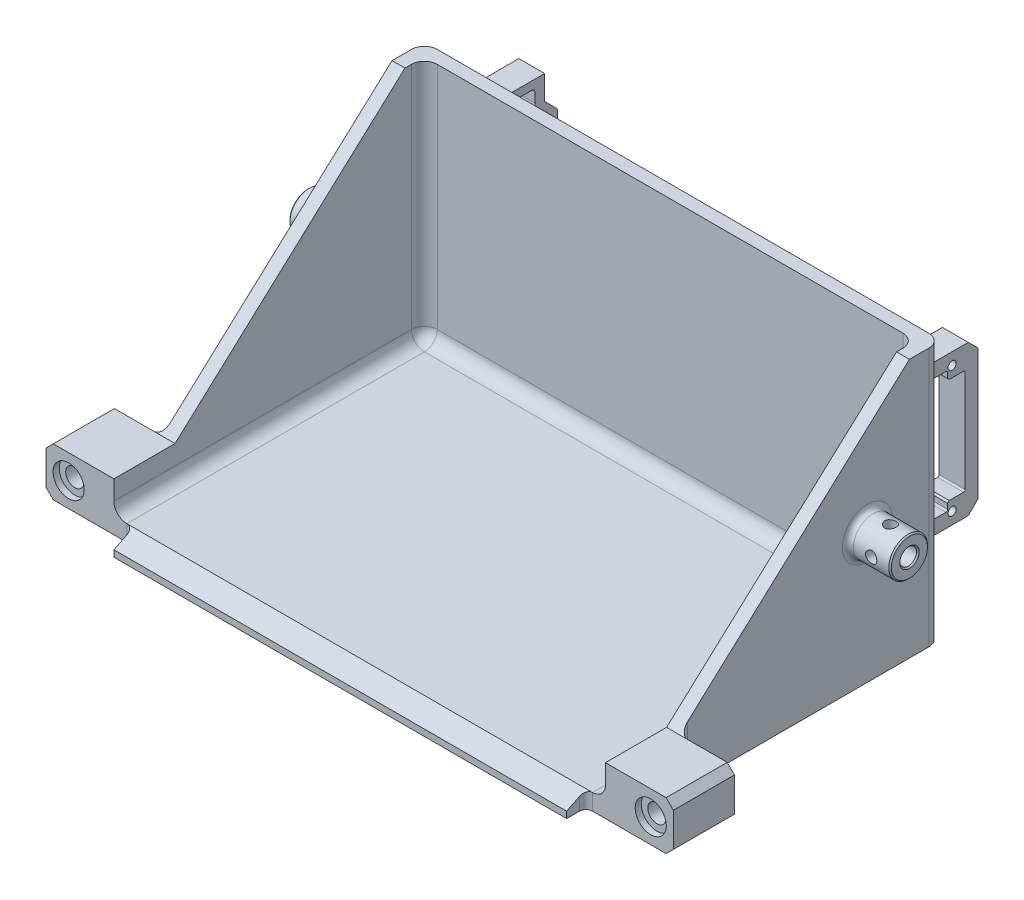
SolidWorks part; units mm, degrees
material "PLA"
ref_plane "Front Plane" through (0, 0, 0) normal (0, 0, 1) x (1, 0, 0)
ref_plane "Top Plane" through (0, 0, 0) normal (0, 1, 0) x (1, 0, 0)
ref_plane "Right Plane" through (0, 0, 0) normal (1, 0, 0) x (0, 0, -1)
sketch "Sketch1" plane through (0, 0, 0) normal (0, 1, 0) x (1, 0, 0)
  line L1 (-101.6, 63.5) -> (101.6, 63.5)
  line L2 (-101.6, 63.5) -> (-101.6, -63.5)
  line L3 (-101.6, -63.5) -> (101.6, -63.5)
  line L4 (101.6, 63.5) -> (101.6, -63.5)
  line L5 (-101.6, 63.5) -> (101.6, -63.5) construction
  line L6 (-101.6, -63.5) -> (101.6, 63.5) construction
  point P0 (0, 0)
  dimension "D1" = 203.2
  dimension "D2" = 127
extrude "Bucket_Base" add sketch "Sketch1" along normal mid plane 6.35
sketch "Sketch3" plane through (-101.6, 0, 0) normal (-1, 0, 0) x (0, 0, 1)
  line L0 (-63.5, 3.175) -> (-63.5, 98.425)
  line L1 (-63.5, 98.425) -> (-50.8, 98.425)
  line L3 (63.5, 3.175) -> (-63.5, 3.175)
  line L4 (-63.5, -3.175) -> (63.5, -3.175) construction
  line L5 (-50.8, 98.425) -> (39.497, 15.875)
  line L6 (39.497, 15.875) -> (63.5, 15.875)
  line L7 (63.5, 15.875) -> (63.5, 3.175)
  dimension "D1" = 101.6
  dimension "D2" = 12.7
  dimension "D3" = 19.05
  dimension "D4" = 24.003
extrude "Bucket_Sides" add sketch "Sketch3" against normal blind 5.08
mirror "Mirror1" about plane through (0, 0, 0) normal (1, 0, 0) of "Bucket_Sides"
sketch "Sketch4" plane through (0, 3.175, 0) normal (0, 1, 0) x (1, 0, 0)
  line L0 (-96.52, 63.5) -> (96.52, 63.5)
  line L1 (96.52, 63.5) -> (96.52, 58.42)
  line L2 (96.52, 58.42) -> (-96.52, 58.42)
  line L3 (-96.52, 58.42) -> (-96.52, 63.5)
  dimension "D1" = 5.08
extrude "Bucket_RearWall" add sketch "Sketch4" along normal up to surface (95.25 mm away) up to face at (-99.06, 98.425, -57.15)
sketch "Sketch6" plane through (101.6, 0, 0) normal (1, 0, 0) x (0, 0, -1)
  line L0 (-63.5, -3.175) -> (63.5, -3.175) construction
  line L2 (63.5, 98.425) -> (63.5, -3.175) construction
  circle A0 centre (34.29, 47.625) radius 3.2893
  circle A1 centre (34.29, 47.625) radius 7.62
  dimension "D1" = 6.5786
  dimension "D2" = 15.24
  dimension "D3" = 50.8
  dimension "D4" = 29.21
extrude "Shaft_Joint" add sketch "Sketch6" along normal blind 16.51
mirror "Mirror2" about plane through (0, 0, 0) normal (1, 0, 0) of "Shaft_Joint"
fillet "Fillet4" radius 2.159 2 edges at (101.6, 47.625, -26.67) (-101.6, 47.625, -41.91)
chamfer "Chamfer1" distance 0.508 angle 45 4 edges at (118.11, 47.625, -37.5793) (118.11, 47.625, -41.91) (-118.11, 47.625, -37.5793) (-118.11, 47.625, -41.91)
ref_plane "setscrew_lhs_plane" through (0, 55.245, 0) normal (0, 1, 0) x (1, 0, 0)
sketch "Sketch7" plane through (0, 55.245, 0) normal (0, 1, 0) x (1, 0, 0)
  line L0 (103.759, 26.67) -> (117.602, 26.67) construction
  line L1 (117.602, 41.91) -> (103.759, 41.91) construction
  line L2 (103.759, 26.67) -> (117.602, 26.67) construction
  line L3 (117.602, 41.91) -> (103.759, 41.91) construction
  line L4 (110.6805, 41.91) -> (110.6805, 26.67) construction
  circle A0 centre (110.6805, 34.29) radius 2.2225
  dimension "D1" = 4.445
extrude "set_screw_holes" cut sketch "Sketch7" against normal blind 6.35
pattern_circular "CirPattern1" count 2 every 90 about axis through (118.11, 47.625, -34.29) along (-1, 0, 0) of "set_screw_holes" reverse direction yes
mirror "Mirror3" about plane through (0, 0, 0) normal (1, 0, 0) of "CirPattern1"
ref_plane "Plane-BearingHousing" through (0, 0, 63.5) normal (0, 0, 1) x (1, 0, 0)
sketch "Sketch12" plane through (0, 0, 63.5) normal (0, 0, 1) x (1, 0, 0)
  line L0 (-101.6, 15.875) -> (-101.6, -3.175) construction
  line L1 (101.6, -3.175) -> (-101.6, -3.175) construction
  line L4 (-114.3, 6.35) -> (-101.6, 6.35) construction
  line L5 (-101.6, 15.875) -> (-101.6, -3.175)
  line L6 (-101.6, 15.875) -> (-123.19, 15.875)
  line L7 (-123.19, 15.875) -> (-123.19, -3.175)
  line L8 (-123.19, -3.175) -> (-101.6, -3.175)
  line L9 (0, -3.175) -> (0, 49996.825) construction
  line L10 (-101.6, 98.425) -> (-101.6, -3.175) construction
  line L11 (-101.6, -3.175) -> (101.6, -3.175) construction
  circle A0 centre (-114.3, 6.35) radius 3.5687
  point P15 (0, -3.175)
  dimension "D1" = 7.1374
  dimension "D2" = 21.59
  dimension "D3" = 114.3
  dimension "D4" = 9.525
extrude "Linear_Bearing_Housing" add sketch "Sketch12" against normal blind 24
mirror "Mirror4" about plane through (0, 0, 0) normal (1, 0, 0) of "Linear_Bearing_Housing"
chamfer "Chamfer2" distance 2.8575 angle 45 4 edges at (123.19, -3.175, 51.5) (123.19, 15.875, 51.5) (-123.19, -3.175, 51.5) (-123.19, 15.875, 51.5)
sketch "ProfilSketch-Servo" plane through (-101.6, 0, 0) normal (-1, 0, 0) x (0, 0, 1)
  line L0 (63.5, 6.35) -> (39.5, 6.35) construction
  line L1 (48.1096, 6.35) -> (-49951.8904, 6.35) construction
  line L2 (-66.421, 69.215) -> (-86.4108, 69.215) construction
  line L3 (-86.4108, 69.215) -> (-86.4108, 29.21) construction
  line L4 (39.5, 13.0175) -> (39.5, -0.3175)
  line L5 (39.5, -0.3175) -> (63.5, -0.3175)
  line L6 (63.5, -0.3175) -> (63.5, 13.0175)
  line L7 (63.5, 13.0175) -> (39.5, 13.0175)
  line L8 (39.5, 13.0175) -> (39.5, -0.3175) construction
  line L9 (39.5, -0.3175) -> (63.5, -0.3175) construction
  line L10 (63.5, -0.3175) -> (63.5, 13.0175) construction
  line L11 (63.5, 13.0175) -> (39.5, 13.0175) construction
  line L12 (-86.4108, 29.21) -> (-66.421, 29.21) construction
  line L13 (-66.421, 29.21) -> (-66.421, 69.215) construction
  line L14 (-63.5, 98.425) -> (-63.5, -3.175) construction
  line L15 (-76.4159, 69.215) -> (-76.4159, 29.21) construction
  line L16 (-81.5213, 24.4602) -> (-71.3105, 24.4602) construction
  line L17 (-76.4159, 24.4602) -> (-76.4159, 29.21) construction
  line L18 (-86.4108, 49.2125) -> (-66.421, 49.2125) construction
  line L19 (-76.4159, 53.2034) -> (-76.4159, 21.1994) construction
  circle A0 centre (-76.4159, 37.2014) radius 3.175 construction
  circle A1 centre (-81.5213, 24.4602) radius 2.2606 construction
  circle A2 centre (-71.3105, 24.4602) radius 2.2606 construction
  circle A3 centre (-71.3105, 73.9648) radius 2.2606 construction
  circle A4 centre (-81.5213, 73.9648) radius 2.2606 construction
  point P32 (-76.4159, 37.2014)
  dimension "D6" = 6.35
  dimension "D10" = 4.5212
  dimension "D11" = 4.5212
  dimension "D2" = 40.005
  dimension "D3" = 19.9898
  dimension "D4" = 2.921
  dimension "D5" = 7.9914
  dimension "D7" = 22.86
  dimension "D8" = 4.7498
  dimension "D9" = 10.2108
  dimension "D12" = 32.004
  dimension "D1" = 0
ref_plane "Servo-Mount-Plane" through (-87.63, 0, 0) normal (-1, 0, 0) x (0, 0, 1)
sketch "Sketch14" plane through (-87.63, 0, 0) normal (-1, 0, 0) x (0, 0, 1)
  line L0 (-86.4108, 49.2125) -> (-66.421, 49.2125) construction
  line L1 (-86.4108, 49.2125) -> (-66.421, 49.2125) construction
  line L2 (-63.5, 19.7485) -> (-91.694, 19.7485)
  line L3 (-63.5, 98.425) -> (-63.5, -3.175) construction
  line L4 (-91.694, 19.7485) -> (-91.694, 78.6765)
  line L5 (-63.5, 19.7485) -> (-63.5, 78.6765)
  line L7 (-66.04, 69.7865) -> (-66.04, 28.6385)
  line L8 (-66.04, 28.6385) -> (-86.614, 28.6385)
  line L9 (-86.614, 28.6385) -> (-86.614, 69.7865)
  line L12 (-63.5, 78.6765) -> (-91.694, 78.6765)
  line L13 (-66.04, 69.7865) -> (-86.614, 69.7865)
  line L14 (-76.327, 69.7865) -> (-76.327, 28.6385) construction
  circle A4 centre (-81.534, 73.9775) radius 1.6129
  circle A5 centre (-71.12, 73.9775) radius 1.6129
  circle A6 centre (-71.12, 24.4475) radius 1.6129
  circle A7 centre (-81.534, 24.4475) radius 1.6129
  point P19 (-91.694, 49.2125)
  point P30 (-63.5, 49.2125)
  point P31 (-66.04, 49.2125)
  point P32 (-86.614, 49.2125)
  dimension "D2" = 41.148
  dimension "D3" = 2.54
  dimension "D6" = 3.2258
  dimension "D8" = 49.53
  dimension "D1" = 20.574
  dimension "D4" = 5.08
  dimension "D5" = 8.89
  dimension "D7" = 10.414
extrude "Servo-Mount" add sketch "Sketch14" against normal blind 10.16
ref_plane "MidPlane-ServoHousing" through (0, 0, -76.327) normal (0, 0, -1) x (-1, 0, 0)
ref_plane "MidPlane2-ServoHousing" through (0, 49.2125, 0) normal (0, 1, 0) x (1, 0, 0)
fillet "Fillet5" radius 1.27 2 edges at (-77.47, 49.2125, -63.5) (-87.63, 49.2125, -63.5)
fillet "Fillet6" radius 5.08 7 edges at (-96.52, 50.8, -58.42) (96.52, 50.8, -58.42) (96.52, 3.175, 2.54) (-96.52, 3.175, 2.54) (0, 3.175, -58.42) (101.6, 47.625, -63.5) (-101.6, 47.625, -63.5)
fillet "Fillet7" radius 3.175 2 edges at (101.6, 6.35, 39.5) (-101.6, 6.35, 39.5)
chamfer "Chamfer4" distance 5.08 angle 45 2 edges at (-82.55, 19.7485, -91.694) (-82.55, 78.6765, -91.694)
sketch "Sketch15" plane through (0, 0, 0) normal (1, 0, 0) x (0, 0, -1)
  line L0 (-63.5, 3.175) -> (53.34, 3.175) construction
  line L1 (-63.5, 3.175) -> (53.34, 3.175) construction
  line L2 (-63.5, 3.175) -> (-71.12, -0.635)
  line L3 (-71.12, -0.635) -> (-71.12, -3.175)
  line L4 (-71.12, -3.175) -> (-63.5, -3.175)
  line L5 (-63.5, 3.175) -> (-63.5, -3.175)
  dimension "D1" = 2.54
  dimension "D2" = 7.62
extrude "Boss-Extrude2" add sketch "Sketch15" along normal mid plane 177.8
fillet "Fillet8" radius 2.54 2 edges at (88.9, 0, 63.5) (-88.9, 0, 63.5)
sketch "Sketch16" plane through (0, 49.2125, 0) normal (0, 1, 0) x (1, 0, 0)
  line L0 (-33.02, 63.5) -> (-33.02, 69.85)
  line L1 (96.52, 63.5) -> (-96.52, 63.5) construction
  line L2 (-33.02, 69.85) -> (-48.26, 69.85)
  line L3 (-48.26, 69.85) -> (-48.26, 66.04)
  line L4 (-48.26, 66.04) -> (-52.07, 66.04)
  line L5 (-52.07, 66.04) -> (-52.07, 73.66)
  line L6 (-52.07, 73.66) -> (-29.21, 73.66)
  line L7 (-29.21, 73.66) -> (-29.21, 63.5)
  line L8 (-33.02, 63.5) -> (-29.21, 63.5)
  line L9 (-77.47, 64.77) -> (-77.47, 86.614) construction
  dimension "D1" = 6.35
  dimension "D2" = 3.81
  dimension "D3" = 2.54
  dimension "D4" = 3.81
  dimension "D5" = 3.81
  dimension "D6" = 25.4
  dimension "D7" = 15.24
extrude "Boss-Extrude3" add sketch "Sketch16" along normal mid plane 13.97
fillet "Fillet9" radius 1.905 6 edges at (-48.26, 49.2125, -69.85) (-33.02, 49.2125, -69.85) (-33.02, 49.2125, -63.5) (-31.115, 42.2275, -63.5) (-31.115, 56.1975, -63.5) (-29.21, 49.2125, -63.5)
sketch "Sketch17" plane through (-87.63, 0, 0) normal (-1, 0, 0) x (0, 0, 1)
  line L0 (-86.614, 78.6765) -> (-86.614, 88.2015)
  line L1 (-64.77, 78.6765) -> (-86.614, 78.6765) construction
  line L2 (-86.614, 88.2015) -> (-69.469, 88.2015)
  line L3 (-69.469, 88.2015) -> (-69.469, 80.8355)
  line L4 (-69.469, 80.8355) -> (-72.644, 80.8355)
  line L5 (-72.644, 80.8355) -> (-72.644, 85.0265)
  line L6 (-72.644, 85.0265) -> (-82.804, 85.0265)
  line L7 (-82.804, 85.0265) -> (-82.804, 78.6765)
  line L8 (-82.804, 78.6765) -> (-86.614, 78.6765)
  dimension "D1" = 3.81
  dimension "D2" = 3.175
  dimension "0.4" = 10.16
  dimension "D4" = 3.175
  dimension "D5" = 6.35
  dimension "D6" = 2.159
extrude "Boss-Extrude4" add sketch "Sketch17" against normal up to surface (10.16 mm away) up to face at (-77.47, 24.4475, -83.1469)
fillet "Fillet10" radius 1.27 4 edges at (-82.55, 78.6765, -86.614) (-82.55, 85.0265, -72.644) (-82.55, 85.0265, -82.804) (-82.55, 78.6765, -82.804)
fillet "Fillet11" radius 0.635 4 edges at (-82.55, 69.7865, -66.04) (-82.55, 69.7865, -86.614) (-82.55, 28.6385, -86.614) (-82.55, 28.6385, -66.04)
sketch "Sketch18" plane through (-87.63, 0, 0) normal (-1, 0, 0) x (0, 0, 1)
  line L0 (-76.327, 69.7865) -> (-76.327, 28.6385) construction
  line L1 (-66.675, 69.7865) -> (-85.979, 69.7865) construction
  line L2 (-85.979, 28.6385) -> (-66.675, 28.6385) construction
  line L3 (-79.756, 69.7865) -> (-79.756, 73.1393)
  line L4 (-79.756, 73.1393) -> (-72.898, 73.1393)
  line L5 (-72.898, 69.7865) -> (-79.756, 69.7865)
  line L6 (-72.898, 69.7865) -> (-72.898, 73.1393)
  line L7 (-76.327, 49.2125) -> (-86.614, 49.2125) construction
  line L8 (-86.614, 69.1515) -> (-86.614, 29.2735) construction
  line L9 (-72.898, 28.6385) -> (-72.898, 25.2857)
  line L10 (-72.898, 28.6385) -> (-79.756, 28.6385)
  line L11 (-79.756, 25.2857) -> (-72.898, 25.2857)
  line L12 (-79.756, 28.6385) -> (-79.756, 25.2857)
  point P11 (-76.327, 73.1393)
  point P19 (-76.327, 25.2857)
  dimension "D1" = 3.3528
  dimension "D2" = 6.858
extrude "Servo-Wire-Relief" cut sketch "Sketch18" against normal through all
fillet "Fillet12" radius 1.016 4 edges at (-82.55, 25.2857, -79.756) (-82.55, 25.2857, -72.898) (-82.55, 73.1393, -79.756) (-82.55, 73.1393, -72.898)
chamfer "Chamfer5" distance 0.635 angle 45 4 edges at (-82.55, 28.6385, -72.898) (-82.55, 28.6385, -79.756) (-82.55, 69.7865, -79.756) (-82.55, 69.7865, -72.898)
sketch "Sketch19" plane through (0, 0, 63.5) normal (0, 0, 1) x (1, 0, 0)
  line L0 (-123.19, 6.35) -> (123.19, 6.35) construction
  line L1 (123.19, 13.0175) -> (123.19, -0.3175) construction
  line L2 (-123.19, 13.0175) -> (-123.19, -0.3175) construction
  line L3 (0, 6.35) -> (0, 50006.35) construction
  circle A0 centre (-114.3, 6.35) radius 6.1087
  circle A1 centre (114.3, 6.35) radius 6.1087
  point P12 (0, 6.35)
  dimension "D1" = 12.2174
extrude "Cut-Extrude2" cut sketch "Sketch19" against normal blind 2.413
ref_plane "LinearBearing_MidPlane" through (0, 0, 51.5) normal (0, 0, 1) x (1, 0, 0)
mirror "Mirror5" about plane through (0, 0, 51.5) normal (0, 0, 1) of "Cut-Extrude2"
mirror "Mirror7" about plane through (0, 0, 0) normal (1, 0, 0) of "Servo-Mount"
fillet "Fillet13" radius 1.27 2 edges at (77.47, 49.2125, -63.5) (87.63, 49.2125, -63.5)
fillet "Fillet14" radius 3.81 4 edges at (-82.55, 19.7485, -63.5) (82.55, 19.7485, -63.5) (-82.55, 78.6765, -63.5) (82.55, 78.6765, -63.5)
mirror "Mirror11" about plane through (0, 0, 0) normal (1, 0, 0) of "Servo-Wire-Relief"
fillet "Fillet15" radius 0.635 4 edges at (82.55, 69.7865, -86.614) (82.55, 69.7865, -66.04) (82.55, 28.6385, -86.614) (82.55, 28.6385, -66.04)
chamfer "Chamfer6" distance 0.635 angle 45 4 edges at (82.55, 69.7865, -79.756) (82.55, 69.7865, -72.898) (82.55, 28.6385, -79.756) (82.55, 28.6385, -72.898)
fillet "Fillet16" radius 0.635 8 edges at (82.55, 73.1393, -79.756) (82.55, 73.1393, -72.898) (82.55, 25.2857, -72.898) (82.55, 25.2857, -79.756) (-82.55, 25.2857, -79.756) (-82.55, 25.2857, -72.898) (-82.55, 73.1393, -79.756) (-82.55, 73.1393, -72.898)
chamfer "Chamfer7" distance 3.81 angle 45 2 edges at (82.55, 19.7485, -91.694) (82.55, 78.6765, -91.694)
equation "\"D11@ProfilSketch-Servo\"=\"D10@ProfilSketch-Servo\""
